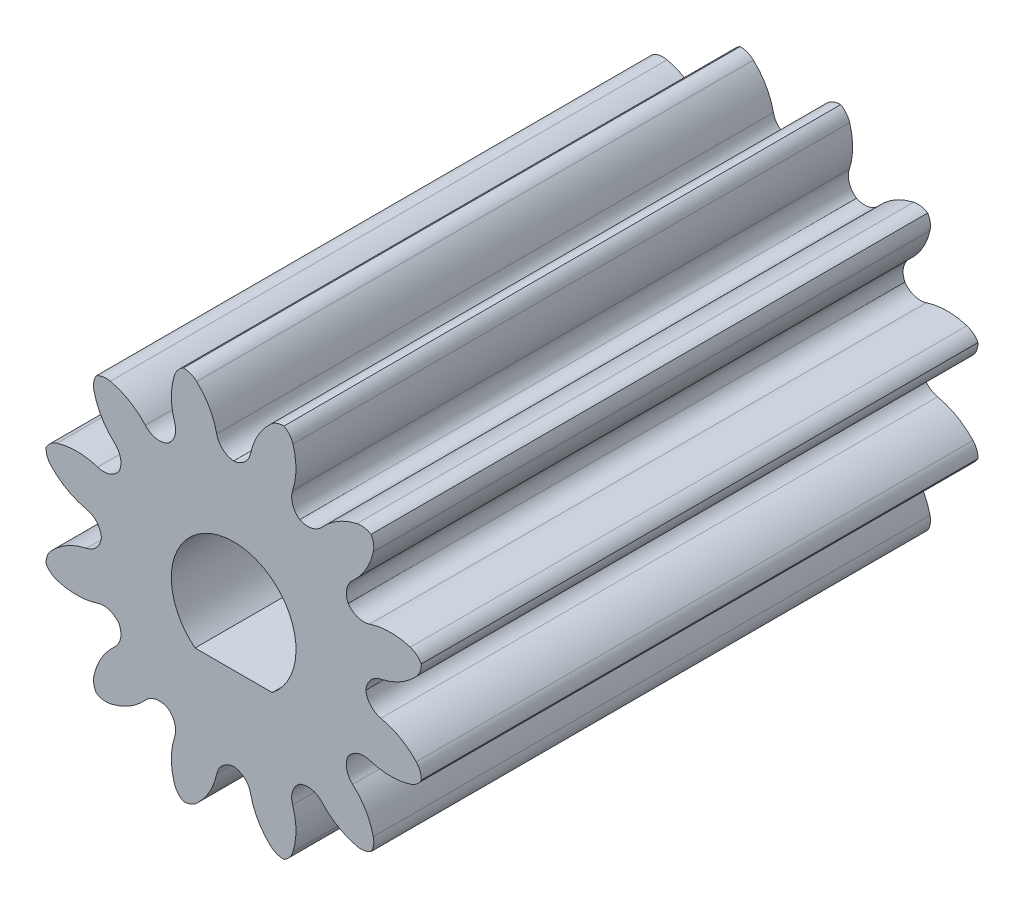
SolidWorks part; units mm, degrees
ref_plane "Front Plane" through (0, 0, 0) normal (0, 0, 1) x (1, 0, 0)
ref_plane "Top Plane" through (0, 0, 0) normal (0, 1, 0) x (1, 0, 0)
ref_plane "Right Plane" through (0, 0, 0) normal (1, 0, 0) x (0, 0, -1)
sketch "Sketch2" plane through (0, 0, 0) normal (0, 0, 1) x (1, 0, 0)
  arc A60 (5.455, -2.342) -> (8.3916, -2.4785) centre (7.0448, 0.2021) ccw
  arc A61 (8.3916, -2.4785) -> (8.5066, -2.0493) centre (0, 0) ccw
  arc A62 (8.5066, -2.0493) -> (5.8952, -0.6993) centre (5.9999, -3.6975) ccw
  arc A63 (5.8952, -0.6993) -> (5.8952, 0.6993) centre (0, 0) ccw
  arc A64 (5.8952, 0.6993) -> (8.5066, 2.0493) centre (5.9999, 3.6975) ccw
  arc A65 (8.5066, 2.0493) -> (8.3916, 2.4785) centre (0, 0) ccw
  arc A66 (8.3916, 2.4785) -> (5.455, 2.342) centre (7.0448, -0.2021) ccw
  arc A67 (5.455, 2.342) -> (4.7557, 3.5532) centre (0, 0) ccw
  arc A68 (4.7557, 3.5532) -> (6.3423, 6.0281) centre (3.3473, 6.202) ccw
  arc A69 (6.3423, 6.0281) -> (6.0281, 6.3423) centre (0, 0) ccw
  arc A70 (6.0281, 6.3423) -> (3.5532, 4.7557) centre (6.202, 3.3473) ccw
  arc A71 (3.5532, 4.7557) -> (2.342, 5.455) centre (0, 0) ccw
  arc A72 (2.342, 5.455) -> (2.4785, 8.3916) centre (-0.2021, 7.0448) ccw
  arc A73 (2.4785, 8.3916) -> (2.0493, 8.5066) centre (0, 0) ccw
  arc A74 (2.0493, 8.5066) -> (0.6993, 5.8952) centre (3.6975, 5.9999) ccw
  arc A75 (0.6993, 5.8952) -> (-0.6993, 5.8952) centre (0, 0) ccw
  arc A76 (-0.6993, 5.8952) -> (-2.0493, 8.5066) centre (-3.6975, 5.9999) ccw
  arc A77 (-2.0493, 8.5066) -> (-2.4785, 8.3916) centre (0, 0) ccw
  arc A78 (-2.4785, 8.3916) -> (-2.342, 5.455) centre (0.2021, 7.0448) ccw
  arc A79 (-2.342, 5.455) -> (-3.5532, 4.7557) centre (0, 0) ccw
  arc A80 (-3.5532, 4.7557) -> (-6.0281, 6.3423) centre (-6.202, 3.3473) ccw
  arc A81 (-6.0281, 6.3423) -> (-6.3423, 6.0281) centre (0, 0) ccw
  arc A82 (-6.3423, 6.0281) -> (-4.7557, 3.5532) centre (-3.3473, 6.202) ccw
  arc A83 (-4.7557, 3.5532) -> (-5.455, 2.342) centre (0, 0) ccw
  arc A84 (-5.455, 2.342) -> (-8.3916, 2.4785) centre (-7.0448, -0.2021) ccw
  arc A85 (-8.3916, 2.4785) -> (-8.5066, 2.0493) centre (0, 0) ccw
  arc A86 (-8.5066, 2.0493) -> (-5.8952, 0.6993) centre (-5.9999, 3.6975) ccw
  arc A87 (-5.8952, 0.6993) -> (-5.8952, -0.6993) centre (0, 0) ccw
  arc A88 (-5.8952, -0.6993) -> (-8.5066, -2.0493) centre (-5.9999, -3.6975) ccw
  arc A89 (-8.5066, -2.0493) -> (-8.3916, -2.4785) centre (0, 0) ccw
  arc A90 (-8.3916, -2.4785) -> (-5.455, -2.342) centre (-7.0448, 0.2021) ccw
  arc A91 (-5.455, -2.342) -> (-4.7557, -3.5532) centre (0, 0) ccw
  arc A92 (-4.7557, -3.5532) -> (-6.3423, -6.0281) centre (-3.3473, -6.202) ccw
  arc A93 (-6.3423, -6.0281) -> (-6.0281, -6.3423) centre (0, 0) ccw
  arc A94 (-6.0281, -6.3423) -> (-3.5532, -4.7557) centre (-6.202, -3.3473) ccw
  arc A95 (-3.5532, -4.7557) -> (-2.342, -5.455) centre (0, 0) ccw
  arc A96 (-2.342, -5.455) -> (-2.4785, -8.3916) centre (0.2021, -7.0448) ccw
  arc A97 (-2.4785, -8.3916) -> (-2.0493, -8.5066) centre (0, 0) ccw
  arc A98 (-2.0493, -8.5066) -> (-0.6993, -5.8952) centre (-3.6975, -5.9999) ccw
  arc A99 (-0.6993, -5.8952) -> (0.6993, -5.8952) centre (0, 0) ccw
  arc A100 (0.6993, -5.8952) -> (2.0493, -8.5066) centre (3.6975, -5.9999) ccw
  arc A101 (2.0493, -8.5066) -> (2.4785, -8.3916) centre (0, 0) ccw
  arc A102 (2.4785, -8.3916) -> (2.342, -5.455) centre (-0.2021, -7.0448) ccw
  arc A103 (2.342, -5.455) -> (3.5532, -4.7557) centre (0, 0) ccw
  arc A104 (3.5532, -4.7557) -> (6.0281, -6.3423) centre (6.202, -3.3473) ccw
  arc A105 (6.0281, -6.3423) -> (6.3423, -6.0281) centre (0, 0) ccw
  arc A106 (6.3423, -6.0281) -> (4.7557, -3.5532) centre (3.3473, -6.202) ccw
  arc A107 (4.7557, -3.5532) -> (5.455, -2.342) centre (0, 0) ccw
extrude "Boss-Extrude1" add sketch "Sketch2" along normal blind 25
fillet "Fillet1" radius 0.85 48 edges at (-2.4785, 8.3916, 12.5) (-2.0493, 8.5066, 12.5) (-0.6993, 5.8952, 12.5) (0.6993, 5.8952, 12.5) (2.0493, 8.5066, 12.5) (2.4785, 8.3916, 12.5) (2.342, 5.455, 12.5) (3.5532, 4.7557, 12.5) (6.0281, 6.3423, 12.5) (6.3423, 6.0281, 12.5) (4.7557, 3.5532, 12.5) (5.455, 2.342, 12.5) (8.3916, 2.4785, 12.5) (8.5066, 2.0493, 12.5) (5.8952, 0.6993, 12.5) (5.8952, -0.6993, 12.5) (8.5066, -2.0493, 12.5) (8.3916, -2.4785, 12.5) (5.455, -2.342, 12.5) (4.7557, -3.5532, 12.5) (6.3423, -6.0281, 12.5) (6.0281, -6.3423, 12.5) (3.5532, -4.7557, 12.5) (2.342, -5.455, 12.5) (2.4785, -8.3916, 12.5) (2.0493, -8.5066, 12.5) (0.6993, -5.8952, 12.5) (-0.6993, -5.8952, 12.5) (-2.0493, -8.5066, 12.5) (-2.4785, -8.3916, 12.5) (-2.342, -5.455, 12.5) (-3.5532, -4.7557, 12.5) (-6.0281, -6.3423, 12.5) (-6.3423, -6.0281, 12.5) (-4.7557, -3.5532, 12.5) (-5.455, -2.342, 12.5) (-8.5066, -2.0493, 12.5) (-5.8952, -0.6993, 12.5) (-5.8952, 0.6993, 12.5) (-8.5066, 2.0493, 12.5) (-8.3916, 2.4785, 12.5) (-5.455, 2.342, 12.5) (-4.7557, 3.5532, 12.5) (-6.3423, 6.0281, 12.5) (-6.0281, 6.3423, 12.5) (-3.5532, 4.7557, 12.5) (-2.342, 5.455, 12.5) (-8.3916, -2.4785, 12.5)
sketch "Sketch3" plane through (0, 0, 0) normal (0, 0, -1) x (-1, 0, 0)
  line L0 (-1.6248, -1.9) -> (1.6248, -1.9) construction
  line L1 (-1.7321, -2.2) -> (1.7321, -2.2)
  arc A1 (-1.6248, -1.9) -> (1.6248, -1.9) centre (0, 0) cw construction
  arc A2 (-1.7321, -2.2) -> (1.7321, -2.2) centre (0, 0) cw
  dimension "D1" = 2.5
  dimension "D4" = 0.3
  dimension "D2" = 4.4
  dimension "D3" = 0.3
extrude "Cut-Extrude1" cut sketch "Sketch3" against normal through all both and the other way through all
chamfer "Chamfer1" distance 2 angle 20 2 edges at (0, -2.2, 0) (0, 2.8, 0) first distance on face at (0, -2.2, 12.5) first distance on face at (0, 0.3, 12.5)
